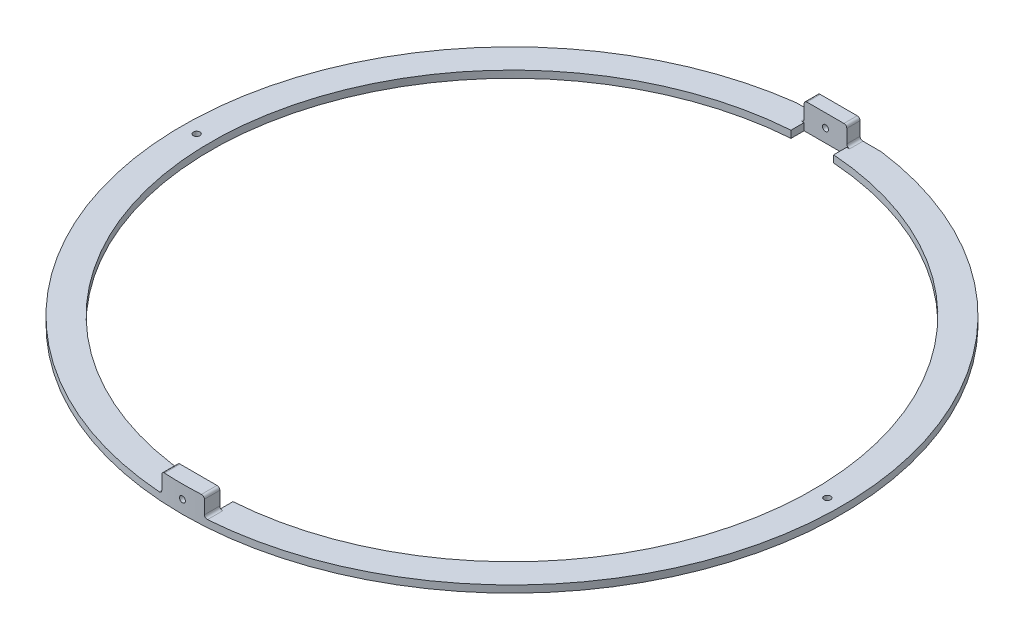
SolidWorks part; units mm, degrees
ref_plane "Front Plane" through (0, 0, 0) normal (0, 0, 1) x (1, 0, 0)
ref_plane "Top Plane" through (0, 0, 0) normal (0, 1, 0) x (1, 0, 0)
ref_plane "Right Plane" through (0, 0, 0) normal (1, 0, 0) x (0, 0, -1)
sketch "Sketch2" plane through (0, 0, 0) normal (0, 1, 0) x (1, 0, 0)
  line L0 (-7.5, 105.6391) -> (-7.5, 110.25)
  line L1 (-7.5, -110.25) -> (7.5, -110.25)
  line L2 (-7.5, -110.25) -> (-7.5, -105.6391)
  line L3 (-7.5, 110.25) -> (7.5, 110.25)
  line L4 (7.5, -110.25) -> (7.5, -105.6391)
  line L5 (-105.905, 0) -> (-115.905, 0) construction
  line L6 (105.905, 0) -> (115.905, 0) construction
  line L9 (7.5, 110.25) -> (7.5, 105.6391)
  circle A0 centre (0, 0) radius 115.905
  arc A1 (7.5, -105.6391) -> (7.5, 105.6391) centre (0, 0) ccw
  arc A2 (-7.5, 105.6391) -> (-7.5, -105.6391) centre (0, 0) ccw
  circle A4 centre (-110.905, 0) radius 1.15
  circle A5 centre (110.905, 0) radius 1.15
  dimension "D1" = 220.5
  dimension "D2" = 10
  dimension "D3" = 2.3
  dimension "D4" = 221.81
  dimension "D5" = 15
extrude "Boss-Extrude1" add sketch "Sketch2" along normal blind 2.5
sketch "Sketch3" plane through (0, 2.5, 0) normal (0, 1, 0) x (1, 0, 0)
  line L0 (-115.905, 0) -> (115.905, 0) construction
  circle A0 centre (0, 0) radius 115.905 construction
sketch "Sketch5" plane through (0, 2.5, 0) normal (0, 1, 0) x (1, 0, 0)
  line L0 (-115.905, 0) -> (115.905, 0) construction
  line L1 (-7.5, 110.25) -> (7.5, 110.25)
  line L3 (-7.5, 115.6621) -> (-7.5, 110.25)
  line L5 (7.5, 115.6621) -> (7.5, 110.25)
  line L6 (-7.5, -115.6621) -> (-7.5, -110.25)
  line L7 (-7.5, -110.25) -> (7.5, -110.25)
  line L8 (7.5, -110.25) -> (7.5, -115.6621)
  arc A0 (-7.5, -115.6621) -> (7.5, -115.6621) centre (0, 0) ccw
  arc A1 (7.5, 115.6621) -> (-7.5, 115.6621) centre (0, 0) ccw
  circle A2 centre (0, 0) radius 115.905 construction
extrude "Boss-Extrude2" add sketch "Sketch5" along normal blind 6.75
sketch "Sketch6" plane through (0, 0, 0) normal (0, 0, 1) x (1, 0, 0)
  line L2 (0, 0) -> (0, 4.59) construction
  circle A1 centre (0, 4.59) radius 1.05
  dimension "D1" = 4.59
  dimension "D2" = 2.1
extrude "Cut-Extrude1" cut sketch "Sketch6" against normal through all both and the other way through all
fillet "Fillet1" radius 1 8 edges at (-7.5, 9.25, -112.956) (-7.5, 2.5, -112.956) (7.5, 9.25, -112.956) (7.5, 2.5, -112.956) (7.5, 2.5, 112.956) (7.5, 9.25, 112.956) (-7.5, 9.25, 112.956) (-7.5, 2.5, 112.956)
sketch "Sketch7" plane through (0, 0, 0) normal (0, 1, 0) x (1, 0, 0)
  line L0 (0, -114.9303) -> (0, 114.9303) construction
  line L1 (-15, 114.9303) -> (15, 114.9303)
  line L2 (-15, 114.9303) -> (-15, 124.9303)
  line L3 (-15, 124.9303) -> (15, 124.9303)
  line L4 (15, 114.9303) -> (15, 124.9303)
  line L5 (-15, -114.9303) -> (15, -114.9303)
  line L6 (-15, -114.9303) -> (-15, -124.9303)
  line L7 (-15, -124.9303) -> (15, -124.9303)
  line L8 (15, -114.9303) -> (15, -124.9303)
  arc A0 (8.5, -115.5929) -> (8.5, 115.5929) centre (0, 0) ccw construction
  point P10 (0, 0)
  dimension "D1" = 30
  dimension "D2" = 10
extrude "Cut-Extrude4" cut sketch "Sketch7" against normal through all and the other way through all contours L2 L1 L4 L3
